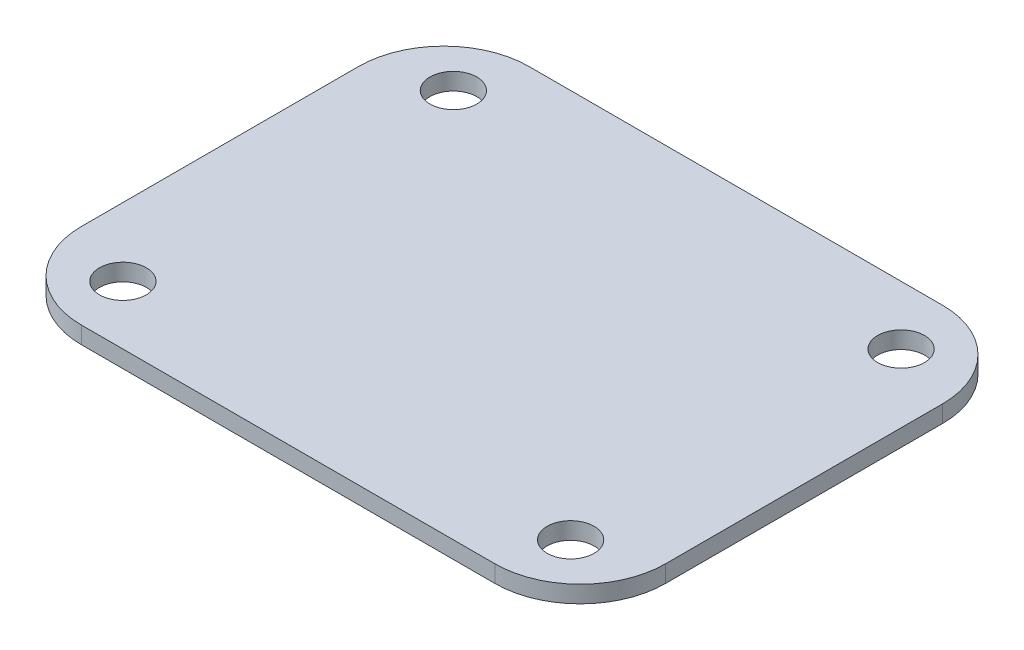
SolidWorks part; units mm, degrees
material "AISI 1020"
ref_plane "Спереди" through (0, 0, 0) normal (0, 0, 1) x (1, 0, 0)
ref_plane "Сверху" through (0, 0, 0) normal (0, 1, 0) x (1, 0, 0)
ref_plane "Справа" through (0, 0, 0) normal (1, 0, 0) x (0, 0, -1)
sketch "Эскиз2" plane through (0, 0, 0) normal (0, 1, 0) x (1, 0, 0)
  line L0 (-48.5, -52.5) -> (48.5, -52.5) construction
  line L1 (-68.5, 32.5) -> (-68.5, -32.5) construction
  line L2 (68.5, -32.5) -> (68.5, 32.5) construction
  line L3 (48.5, 52.5) -> (-48.5, 52.5) construction
  line L4 (-48.5, -52.5) -> (48.5, -52.5)
  line L5 (-68.5, 32.5) -> (-68.5, -32.5)
  line L6 (68.5, -32.5) -> (68.5, 32.5)
  line L7 (48.5, 52.5) -> (-48.5, 52.5)
  line L8 (47, 40) -> (47, 37.5) construction
  line L9 (58, 37.5) -> (58, 40) construction
  line L10 (47, 40) -> (47, 37.5) construction
  line L11 (58, 37.5) -> (58, 40) construction
  line L12 (0, 52.5) -> (0, -52.5) construction
  line L13 (68.5, 0) -> (-68.5, 0) construction
  arc A1 (-68.5, -32.5) -> (-48.5, -52.5) centre (-48.5, -32.5) ccw construction
  arc A2 (-48.5, 52.5) -> (-68.5, 32.5) centre (-48.5, 32.5) ccw construction
  arc A3 (48.5, -52.5) -> (68.5, -32.5) centre (48.5, -32.5) ccw construction
  arc A4 (68.5, 32.5) -> (48.5, 52.5) centre (48.5, 32.5) ccw construction
  arc A5 (-68.5, -32.5) -> (-48.5, -52.5) centre (-48.5, -32.5) ccw
  arc A6 (-48.5, 52.5) -> (-68.5, 32.5) centre (-48.5, 32.5) ccw
  arc A7 (48.5, -52.5) -> (68.5, -32.5) centre (48.5, -32.5) ccw
  arc A8 (68.5, 32.5) -> (48.5, 52.5) centre (48.5, 32.5) ccw
  circle A9 centre (52.5, 38.75) radius 5.5
  circle A10 centre (-52.5, 38.75) radius 5.5
  circle A11 centre (52.5, -38.75) radius 5.5
  circle A12 centre (-52.5, -38.75) radius 5.5
  point P18 (58, 38.75)
base flange "Базовая кромка1" sketch "Эскиз2" thickness 4 reverse thickness direction yes parameters "D1"=0.75
sketch "Сгиб-Линии1" plane through (0, 0, 0) normal (0, 1, 0) x (1, 0, 0)
sketch "Граничная рамка1" plane through (0, 0, 0) normal (0, 1, 0) x (1, 0, 0)
sheet metal parameters "Листовой металл3" thickness 4 parameters "D1"=0.75
flat pattern "Развертка3" [suppressed]
sketch "Сгиб-Линии2" plane through (0, 0, 0) normal (0, 1, 0) x (1, 0, 0)
sketch "Граничная рамка2" [suppressed] plane through (0, 0, 0) normal (0, 1, 0) x (1, 0, 0)
